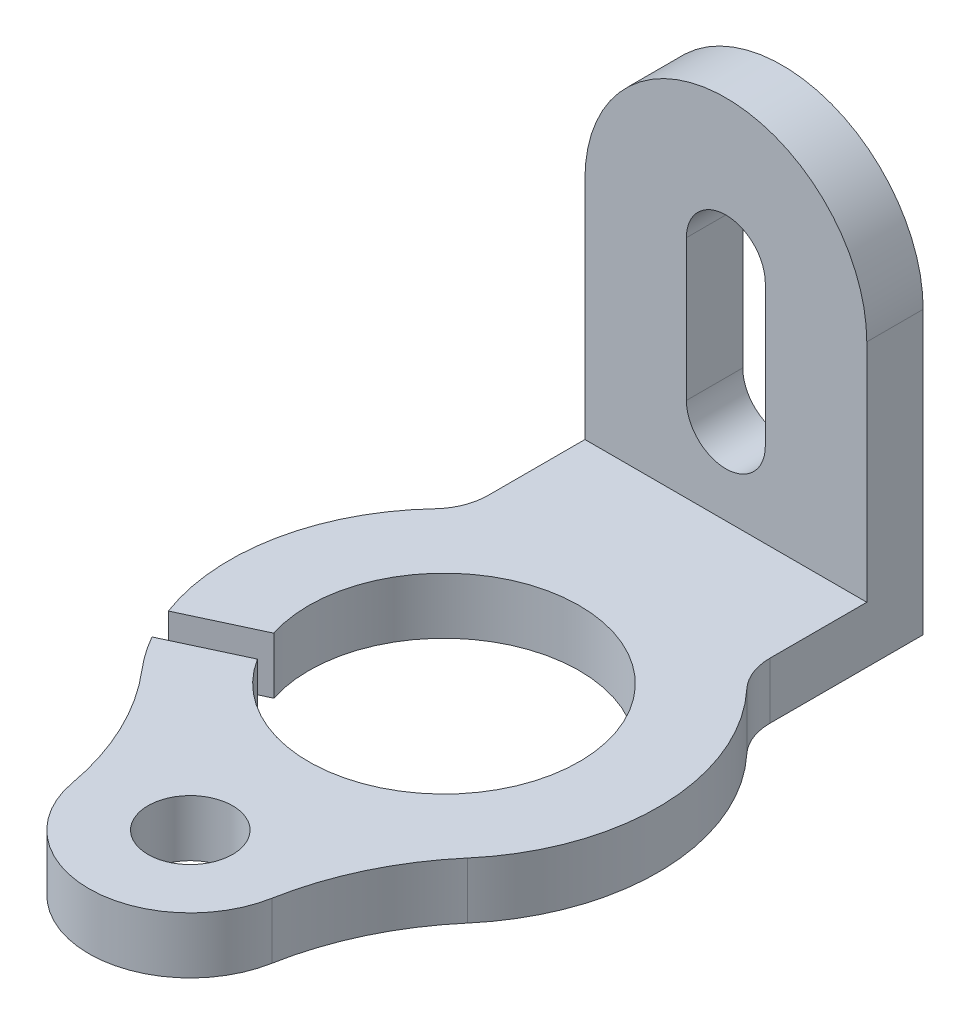
SolidWorks part; units mm, degrees
ref_plane "Front Plane" through (0, 0, 0) normal (0, 0, 1) x (1, 0, 0)
ref_plane "Top Plane" through (0, 0, 0) normal (0, 1, 0) x (1, 0, 0)
ref_plane "Right Plane" through (0, 0, 0) normal (1, 0, 0) x (0, 0, -1)
sketch "Sketch1" plane through (0, 0, 0) normal (0, 1, 0) x (1, 0, 0)
  line L4 (-25, 10) -> (-25, -17.1519)
  line L5 (-25, 10) -> (25, 10)
  line L6 (25, 10) -> (25, -17.1519)
  line L7 (25, 0) -> (-25, 0)
  line L8 (0, 22.5031) -> (0, -181.0963) construction
  line L9 (0, -50) -> (-49.8884, -73.2634) construction
  line L10 (-20.3129, -62.7822) -> (-33.0643, -68.7283)
  line L11 (-22.8486, -57.3444) -> (-35.6001, -63.2904)
  arc A0 (-27.7083, -23.9952) -> (-35.6001, -63.2904) centre (0, -50) ccw
  arc A1 (-20.3129, -62.7822) -> (-22.8486, -57.3444) centre (0, -50) ccw
  arc A2 (-17.7095, -98.2206) -> (17.7095, -98.2206) centre (0, -95) ccw
  circle A3 centre (0, -95) radius 7.5
  arc A4 (-28.8898, -74.6856) -> (-17.7095, -98.2206) centre (-66.9027, -107.1667) cw
  arc A5 (28.8898, -74.6856) -> (17.7095, -98.2206) centre (66.9027, -107.1667) ccw
  arc A6 (25, -17.1519) -> (27.7083, -23.9952) centre (35, -17.1519) ccw
  arc A7 (-25, -17.1519) -> (-27.7083, -23.9952) centre (-35, -17.1519) cw
  arc A8 (28.8898, -74.6856) -> (27.7083, -23.9952) centre (0, -50) ccw
  arc A9 (-33.0643, -68.7283) -> (-28.8898, -74.6856) centre (0, -50) ccw
  point P30 (-49.8884, -73.2634)
  point P31 (-22.8485, -57.3447)
  point P32 (-20.3123, -62.7832)
  point P33 (-33.0643, -68.7283)
  point P34 (-35.7857, -62.7822)
  dimension "D1" = 10
  dimension "D2" = 10
  dimension "D5" = 76
  dimension "D6" = 48
  dimension "D7" = 36
  dimension "D8" = 15
  dimension "D9" = 50
  dimension "D10" = 50
  dimension "D3" = 50
  dimension "D4" = 45
  dimension "D11" = 10
  dimension "D12" = 50
  dimension "D13" = 25
  dimension "D14" = 6
extrude "Boss-Extrude1" add sketch "Sketch1" along normal blind 10 contours L10 A9 A4 A2 A5 A8 A6 L6 L7 L4 A7 A0 L11 A1 A3 region at (0, 0, 1.3618)
extrude "Boss-Extrude2" add sketch "Sketch1<3>" along normal blind 75 contours L7 L6 L5 L4 region at (0, 0, -5)
sketch "Sketch1<3>" plane through (0, 0, 0) normal (0, 1, 0) x (1, 0, 0) same geometry as "Sketch1"
sketch "Sketch2" plane through (0, 0, 0) normal (0, 0, 1) x (1, 0, 0)
  line L0 (25, 75) -> (-25, 75) construction
  line L1 (25, 75) -> (25, 10) construction
  line L2 (-25, 75) -> (-25, 10) construction
  line L3 (0, 50) -> (0, 25) construction
  line L4 (7, 50) -> (7, 25)
  line L5 (-7, 50) -> (-7, 25)
  line L6 (45.1812, 50) -> (-36.6278, 50) construction
  arc A0 (25, 50) -> (-25, 50) centre (0, 50) ccw
  arc A1 (7, 50) -> (-7, 50) centre (0, 50) ccw
  arc A2 (-7, 25) -> (7, 25) centre (0, 25) ccw
  point P10 (0, 37.5)
  line M8 (25, 10) -> (25, 75)
  line M9 (25, 75) -> (-25, 75)
  line M10 (-25, 75) -> (-25, 10)
  dimension "D1" = 25
  dimension "D2" = 7
extrude "Cut-Extrude1" cut sketch "Sketch2" against normal up to next contours L5 A2 L4 A1 | A0 M8 M9 | A0 M9 M10 region at (0, 37.5, 0) region at (-19.4158, 69.4158, 0) region at (19.4158, 69.4158, 0)
